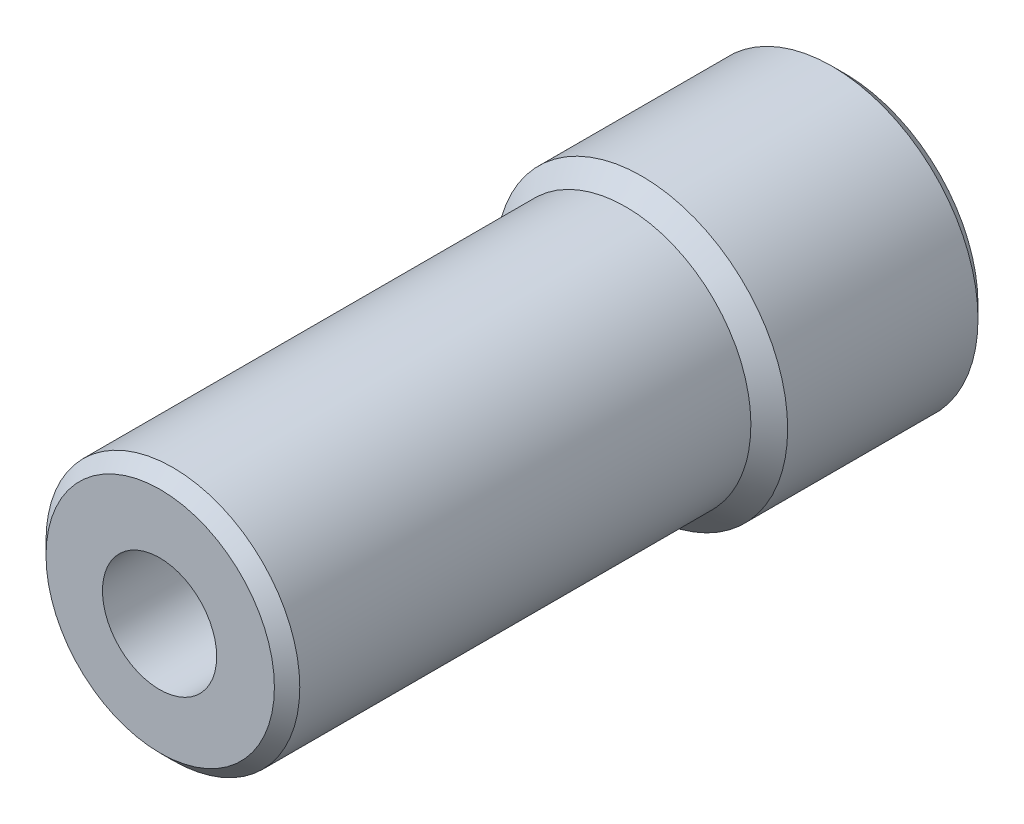
SolidWorks part; units mm, degrees
ref_plane "Front Plane" through (0, 0, 0) normal (0, 0, 1) x (1, 0, 0)
ref_plane "Top Plane" through (0, 0, 0) normal (0, 1, 0) x (1, 0, 0)
ref_plane "Right Plane" through (0, 0, 0) normal (1, 0, 0) x (0, 0, -1)
sketch "Sketch2" plane through (0, 0, 0) normal (0, 0, 1) x (1, 0, 0)
  line L0 (0, -55) -> (0, 55) construction
  circle A0 centre (0, -0.0683) radius 5.75
  dimension "D1" = 11.5
extrude "Boss-Extrude2" add sketch "Sketch2" along normal blind 10
sketch "Sketch3" plane through (0, 0, 10) normal (0, 0, 1) x (1, 0, 0)
  line L0 (5.5, 0) -> (-5.5, 0) construction
  circle A0 centre (0.0249, 0) radius 5
  dimension "D1" = 10
extrude "Boss-Extrude3" add sketch "Sketch3" along normal blind 17
sketch "Sketch4" plane through (0, 0, 0) normal (0, 0, -1) x (-1, 0, 0)
  line L0 (0, 6.325) -> (0, -6.325) construction
  line L1 (6.325, 0) -> (-6.325, 0) construction
  circle A0 centre (0, 0) radius 2.5
  dimension "D1" = 5
extrude "Cut-Extrude1" cut sketch "Sketch4" against normal blind 10.7
sketch "Sketch5" plane through (0, 0, 27) normal (0, 0, 1) x (1, 0, 0)
  line L0 (0, -6.325) -> (0, 6.325) construction
  circle A0 centre (0, -0.0931) radius 2.25
  dimension "D1" = 4.5
extrude "Cut-Extrude2" cut sketch "Sketch5" against normal blind 17.7
chamfer "Chamfer4" distance 2 angle 45 1 edges at (5.75, -0.0683, 10)
chamfer "Chamfer5" distance 0.5 angle 45 1 edges at (5.0249, 0, 27)
chamfer "Chamfer6" distance 0.5 angle 45 1 edges at (5.75, -0.0683, 0)
